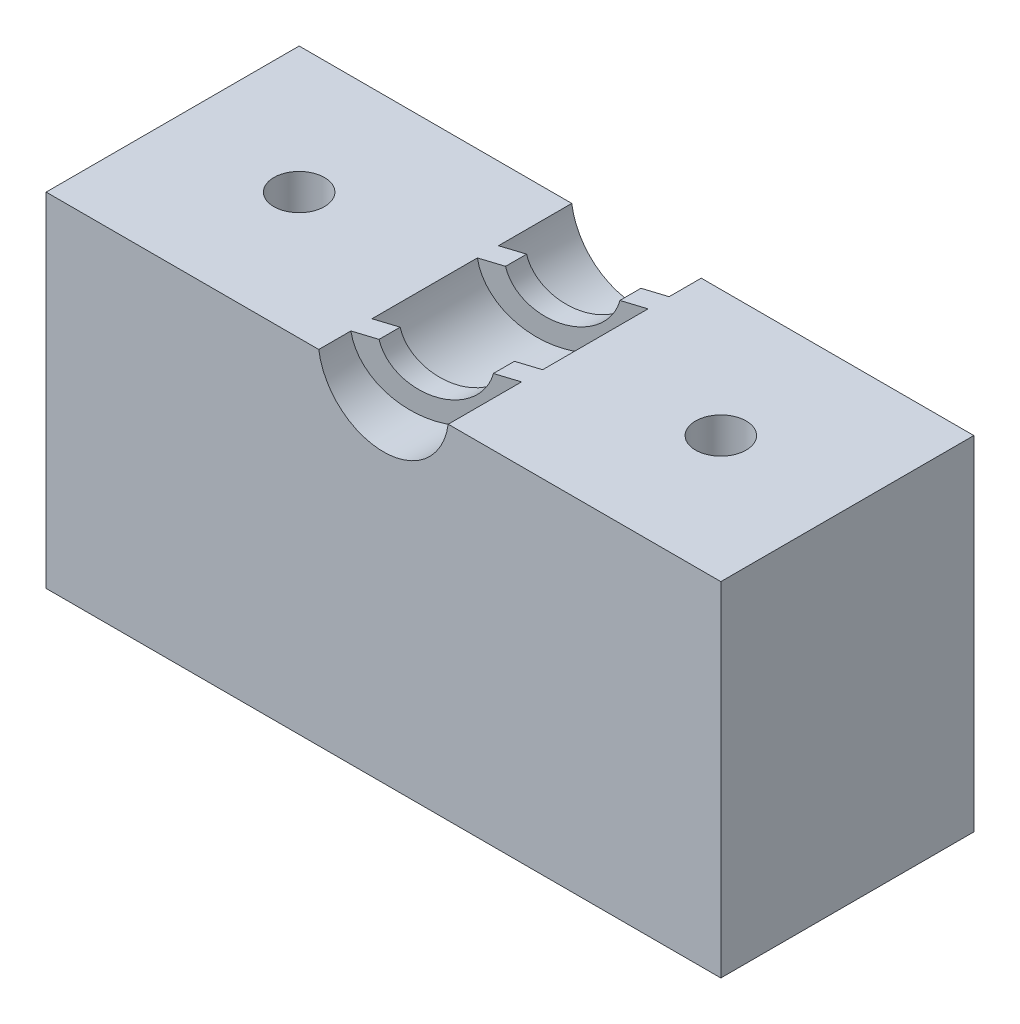
SolidWorks part; units mm, degrees
ref_plane "前视基准面" through (0, 0, 0) normal (0, 0, 1) x (1, 0, 0)
ref_plane "上视基准面" through (0, 0, 0) normal (0, 1, 0) x (1, 0, 0)
ref_plane "右视基准面" through (0, 0, 0) normal (1, 0, 0) x (0, 0, -1)
other "Configuration Table"
sketch "草图1" plane through (0, 0, 0) normal (0, 0, 1) x (1, 0, 0)
  line L1 (-8, -8) -> (8, -8)
  line L2 (-8, -8) -> (-8, 8)
  line L3 (-8, 8) -> (8, 8)
  line L4 (8, -8) -> (8, 8)
  line L5 (-8, -8) -> (8, 8) construction
  line L6 (-8, 8) -> (8, -8) construction
  circle A0 centre (0, 0) radius 1.55
  point P0 (0, 0)
  dimension "D3" = 3.1
  dimension "D1" = 16
  dimension "D2" = 16
extrude "凸台-拉伸1" add sketch "草图1" along normal mid plane 6
sketch "草图6" plane through (0, 0, 0) normal (0, 1, 0) x (1, 0, 0)
  line L0 (-1.55, -3) -> (1.55, -3) construction
  line L1 (1.55, 3) -> (-1.55, 3) construction
  line L2 (-1.55, -3) -> (1.55, -3)
  line L3 (1.55, 3) -> (-1.55, 3)
  line L4 (-1.55, 3) -> (-1.55, -3)
  line L5 (1.55, -3) -> (1.55, 3)
  line L6 (-1.55, 0.7565) -> (1.55, 1.7435)
  line L7 (1.55, 1.7435) -> (1.55, 2.2435)
  line L8 (1.55, 2.2435) -> (-1.55, 1.2565)
  line L9 (-1.55, -1.7435) -> (1.55, -0.7565)
  line L10 (-1.55, -2.2435) -> (1.55, -1.2565)
  line L11 (-2.0945, -0.6668) -> (3.135, 0.9981) construction
  line L12 (-3.1004, 0) -> (4.2723, 0) construction
  dimension "D1" = 2.5
  dimension "D2" = 0.5
  dimension "D3" = 0.5
  dimension "D4" = 17.66
extrude "凸台-拉伸2" add sketch "草图6" against normal up to surface (8 mm away) contours L4 L10 L5 L9 | L5 L8 L4 L6 region at (0, 0, 1.5) region at (0, 0, -1.5)
sketch "草图7" plane through (0, 0, 0) normal (0, 0, 1) x (1, 0, 0)
  line L0 (0, 0) -> (-1.0279, -0.2141)
  line L1 (0, 0) -> (1.0279, -0.2141)
  line L2 (-1.0279, -0.2141) -> (-8, -0.2141)
  line L3 (1.0279, -0.2141) -> (8, -0.2141)
  line L6 (8, -8) -> (8, 8)
  line L7 (-8, -8) -> (8, -8)
  line L8 (-8, 8) -> (-8, -8)
  line L9 (8, 8) -> (-8, 8)
  line L10 (8, -8) -> (8, 8)
  line L11 (-8, -8) -> (8, -8)
  line L12 (-8, 8) -> (-8, -8)
  line L13 (8, 8) -> (-8, 8)
  circle A0 centre (0, 0) radius 1.05
  dimension "D1" = 2.1
  dimension "D2" = 0
  dimension "D3" = 156.47
extrude "切除-拉伸2" cut sketch "草图7" against normal through all both and the other way through all contours A0 L3 L10 L13 L12 L2 | L1 A0 L0 | L0 A0 L1 region at (0, -0.5019, 0) region at (0, 0.3858, 0) region at (0, 3.953, 0)
sketch "草图8" plane through (0, 0, 0) normal (0, 1, 0) x (1, 0, 0)
  line L0 (0, 5.5834) -> (0, -5.0797) construction
  circle A0 centre (-5, 0) radius 0.6
  circle A1 centre (5, 0) radius 0.6
  dimension "D2" = 1.2
  dimension "D3" = 10
extrude "切除-拉伸3" cut sketch "草图8" against normal through all
sketch "草图9" plane through (0, -8, 0) normal (0, -1, 0) x (1, 0, 0)
  line L4 (-8, -3) -> (8, -3)
  line L5 (8, -3) -> (8, 3)
  line L6 (8, 3) -> (-8, 3)
  line L7 (-8, 3) -> (-8, -3)
  line L8 (-8, -3) -> (8, -3)
  line L9 (8, -3) -> (8, 3)
  line L10 (8, 3) -> (-8, 3)
  line L11 (-8, 3) -> (-8, -3)
  circle A0 centre (-5, 0) radius 0.6 construction
  circle A1 centre (5, 0) radius 0.6 construction
  circle A2 centre (-5, 0) radius 0.6
  circle A3 centre (5, 0) radius 0.6
  dimension "D1" = 0
extrude "凸台-拉伸3" add sketch "草图9" along normal offset from surface (0.355 mm away) 0.6
equation "\"x\"=0.8094"
